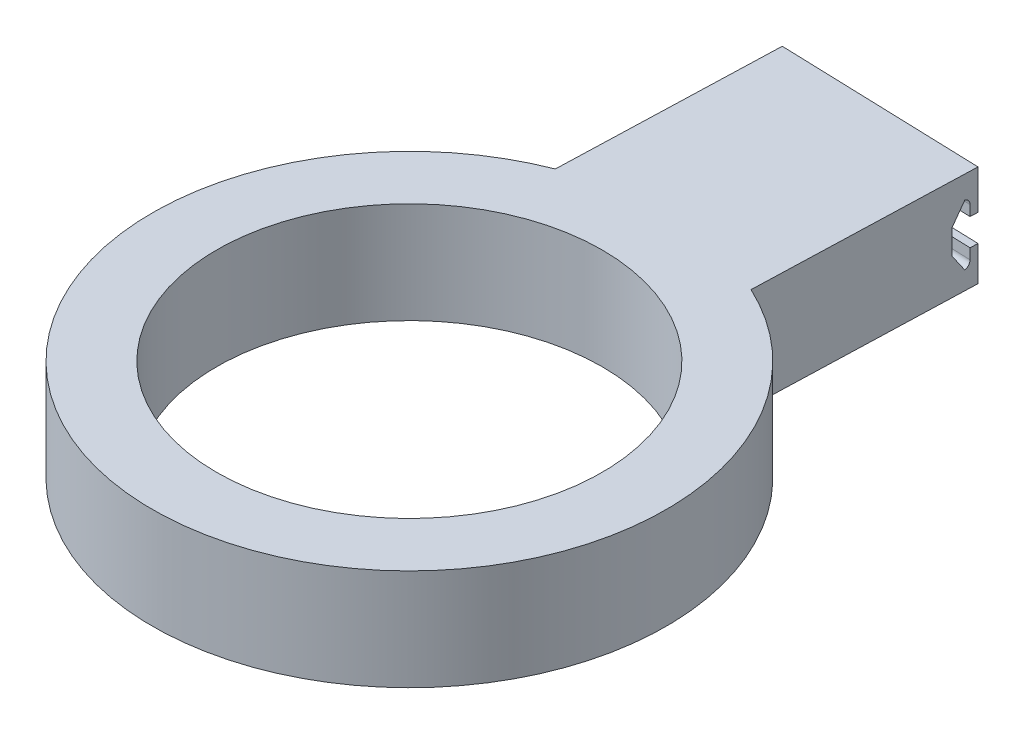
SolidWorks part; units mm, degrees
ref_plane "Front Plane" through (0, 0, 0) normal (0, 0, 1) x (1, 0, 0)
ref_plane "Top Plane" through (0, 0, 0) normal (0, 1, 0) x (1, 0, 0)
ref_plane "Right Plane" through (0, 0, 0) normal (1, 0, 0) x (0, 0, -1)
sketch "Sketch1" plane through (0, 0, 0) normal (0, 1, 0) x (1, 0, 0)
  circle A0 centre (0, 0) radius 38.1
  circle A1 centre (0, 0) radius 50.8
  dimension "D1" = 76.2
  dimension "D2" = 12.7
extrude "Boss-Extrude1" add sketch "Sketch1" along normal blind 20
sketch "Sketch2" plane through (0, 20, 0) normal (0, 1, 0) x (1, 0, 0)
  line L0 (-18.4722, 47.3225) -> (21.5278, 46.013)
  line L1 (-18.4722, 47.3225) -> (-18.1475, 57.2415)
  line L2 (21.5278, 46.013) -> (21.8525, 55.932)
  line L3 (-18.1475, 57.2415) -> (21.8525, 55.932)
  line L4 (-18.3594, 50.7687) -> (21.6406, 49.4592)
  line L5 (-18.3594, 50.7687) -> (-17.0499, 90.7687)
  line L6 (21.6406, 49.4592) -> (22.9501, 89.4592)
  line L7 (-17.0499, 90.7687) -> (22.9501, 89.4592)
  circle A0 centre (0, 0) radius 50.8 construction
  circle M7 centre (0, 0) radius 50.8
  dimension "D1" = 40
  dimension "D2" = 40
extrude "Boss-Extrude2" add sketch "Sketch2" against normal blind 20 contours L4 L2 M7 | L1 L4 L2 L3 M7 | L4 L1 M7 | L7 L5 L3 L6 region at (-14.791, 20, -49.5788) region at (18.002, 20, -48.5053) region at (1.7493, 20, -53.435) region at (2.4013, 20, -73.3504)
sketch "Sketch4" plane through (20, 0, 0.6547) normal (0.9995, 0, 0.0327) x (0.0327, 0, -0.9995)
  line L0 (90.1622, 12.2225) -> (88.6382, 12.2225)
  line L1 (90.1622, 0) -> (90.1622, 20) construction
  line L2 (88.6382, 12.2225) -> (88.6382, 15.5245)
  line L3 (88.6382, 15.5245) -> (87.6222, 15.5245)
  line L4 (87.6222, 15.5245) -> (85.1727, 11.9685)
  line L5 (85.1727, 11.9685) -> (85.1727, 7.1425)
  line L6 (85.1727, 7.1425) -> (87.6222, 3.5865)
  line L7 (87.6222, 3.5865) -> (88.6382, 3.5865)
  line L8 (88.6382, 3.5865) -> (88.6382, 6.8885)
  line L9 (88.6382, 6.8885) -> (90.1622, 6.8885)
  line L10 (90.1622, 6.8885) -> (90.1622, 12.2225)
  point P10 (83.4813, 3.5865)
  dimension "D1" = 5.334
  dimension "D2" = 1.524
  dimension "D3" = 3.302
  dimension "D4" = 3.302
  dimension "D5" = 1.524
  dimension "D6" = 4.318
  dimension "D7" = 1.016
  dimension "D8" = 1.016
  dimension "D9" = 4.318
  dimension "D10" = 4.826
extrude "Cut-Extrude1" cut sketch "Sketch4" against normal through all both and the other way through all
fillet "Fillet1" radius 1.27 2 edges at (2.9002, 3.5865, -88.5907) (2.9002, 15.5245, -88.5907)
